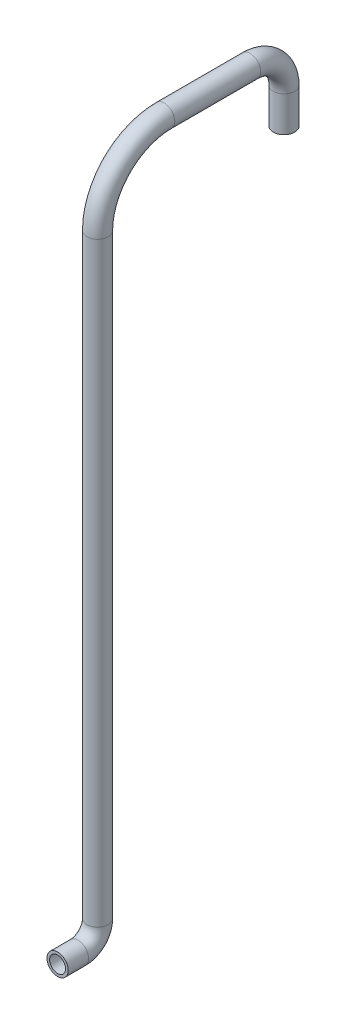
SolidWorks part; units mm, degrees
ref_plane "Front Plane" through (0, 0, 0) normal (0, 0, 1) x (1, 0, 0)
ref_plane "Top Plane" through (0, 0, 0) normal (0, 1, 0) x (1, 0, 0)
ref_plane "Right Plane" through (0, 0, 0) normal (1, 0, 0) x (0, 0, -1)
sketch "Sketch1" plane through (0, 0, 0) normal (0, 0, 1) x (1, 0, 0)
  circle A0 centre (0, 0) radius 4
  circle A1 centre (0, 0) radius 4
sketch3d "3DSketch1"
  line L0 (0, 0, 0) -> (0, 0, -7.65)
  line L1 (0, 7.35, -15) -> (0, 231, -15)
  line L2 (0, 256, -40) -> (0, 256, -72.26)
  line L3 (0, 243.26, -85) -> (0, 230, -85)
  arc A0 (0, 0, -7.65) -> (0, 7.35, -15) centre (0, 7.35, -7.65) cw
  arc A1 (0, 231, -15) -> (0, 256, -40) centre (0, 231, -40) cw
  arc A2 (0, 256, -72.26) -> (0, 243.26, -85) centre (0, 243.26, -72.26) cw
  point P4 (7.35, 7.35, -7.65)
  point P11 (-25, 231, -40)
  point P18 (-12.74, 243.26, -72.26)
sweep "Sweep1" add path "3DSketch1" circular profile diameter 8 parameters "D3"=8
sweep "Hollow_tube_OD_and_wall_PROVISIONAL" cut path "3DSketch1<2>" circular profile diameter 6 parameters "D3"=6
sketch3d "3DSketch1<2>" same geometry as "3DSketch1"
